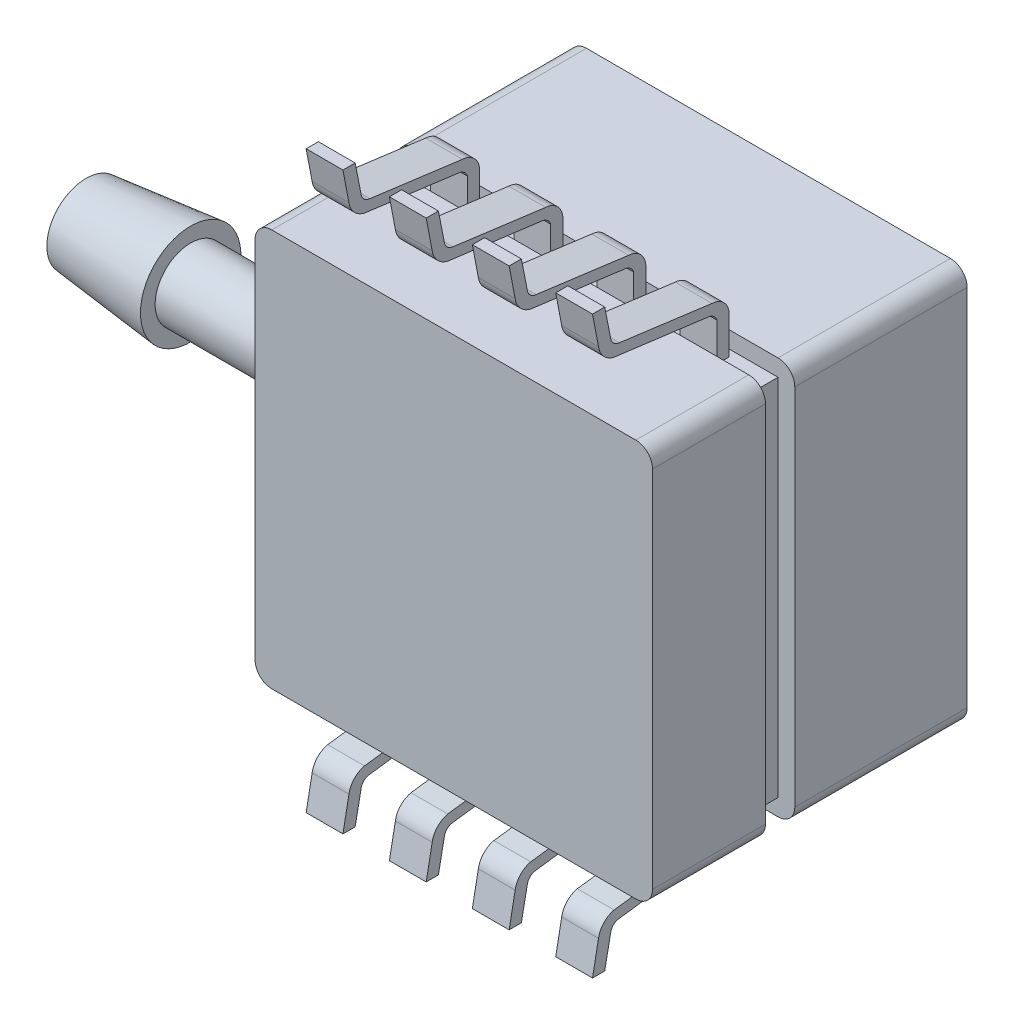
SolidWorks part; units mm, degrees
ref_plane "Front Plane" through (0, 0, 0) normal (0, 0, 1) x (1, 0, 0)
ref_plane "Top Plane" through (0, 0, 0) normal (0, 1, 0) x (1, 0, 0)
ref_plane "Right Plane" through (0, 0, 0) normal (1, 0, 0) x (0, 0, -1)
sketch "Sketch1" plane through (0, 0, 0) normal (0, 0, 1) x (1, 0, 0)
  line L1 (-6.0325, -6.0325) -> (6.0325, -6.0325)
  line L2 (-6.0325, -6.0325) -> (-6.0325, 6.0325)
  line L3 (-6.0325, 6.0325) -> (6.0325, 6.0325)
  line L4 (6.0325, -6.0325) -> (6.0325, 6.0325)
  line L5 (-6.0325, -6.0325) -> (6.0325, 6.0325) construction
  line L6 (-6.0325, 6.0325) -> (6.0325, -6.0325) construction
  point P1 (0, 0)
  dimension "D1" = 12.065
  dimension "D2" = 12.065
extrude "Boss-Extrude1" add sketch "Sketch1" along normal blind 9.5504
sketch "Sketch3" plane through (0, 6.0325, 0) normal (0, 1, 0) x (1, 0, 0)
  line L0 (37.8159, 86.4688) -> (213.1492, 86.4688) construction
  line L1 (-6.0325, -9.5504) -> (-6.0325, 0) construction
  line L2 (-5.5245, -5.2324) -> (-6.0325, -5.2324)
  line L3 (-5.5245, -5.2324) -> (-5.5245, -6.1214)
  line L4 (-5.5245, -6.1214) -> (-6.0325, -6.1214)
  line L5 (-6.0325, -5.2324) -> (-6.0325, -6.1214)
  line L6 (6.0325, -9.5504) -> (-6.0325, -9.5504) construction
  line L7 (0, 0) -> (0, -9.5504) construction
  line L8 (6.0325, -5.2324) -> (6.0325, -6.1214)
  line L9 (5.5245, -6.1214) -> (6.0325, -6.1214)
  line L10 (5.5245, -5.2324) -> (5.5245, -6.1214)
  line L11 (5.5245, -5.2324) -> (6.0325, -5.2324)
  dimension "D1" = 3.429
  dimension "D2" = 0.889
  dimension "D3" = 0.508
extrude "Cut-Extrude1" cut sketch "Sketch3" against normal through all
sketch "Sketch4" plane through (5.5245, 0, 0) normal (1, 0, 0) x (0, 0, -1)
  line L0 (-5.2324, -6.0325) -> (-5.2324, 6.0325) construction
  line L1 (-6.1214, 6.0325) -> (-5.2324, 6.0325)
  line L2 (-6.1214, 6.0325) -> (-6.1214, 5.5245)
  line L3 (-6.1214, 5.5245) -> (-5.2324, 5.5245)
  line L4 (-5.2324, 6.0325) -> (-5.2324, 5.5245)
  line L6 (-6.1214, -6.0325) -> (-5.2324, -6.0325)
  line L7 (-6.1214, -6.0325) -> (-6.1214, -5.5245)
  line L8 (-6.1214, -5.5245) -> (-5.2324, -5.5245)
  line L9 (-5.2324, -6.0325) -> (-5.2324, -5.5245)
  dimension "D1" = 0.508
  dimension "D2" = 0.508
extrude "Cut-Extrude2" cut sketch "Sketch4" against normal through all
sketch "Sketch5" plane through (6.0325, 0, 0) normal (1, 0, 0) x (0, 0, -1)
  line L0 (120.7784, 207.8165) -> (628.7784, 207.8165) construction
  line L1 (-5.4408, 5.5245) -> (-5.4408, 6.6427)
  line L2 (-6.1214, 5.5245) -> (-5.2324, 5.5245) construction
  line L3 (-5.8107, 5.5245) -> (-5.8107, 6.6769)
  line L4 (-6.0874, 6.8958) -> (-8.9346, 7.2659)
  line L5 (-5.9608, 7.194) -> (-8.7733, 7.5656)
  line L6 (-9.2194, 8.727) -> (-9.031, 7.774)
  line L7 (-9.5894, 8.727) -> (-9.4077, 7.774)
  line L8 (-9.2194, 8.727) -> (-9.5894, 8.727)
  line L9 (0, 0) -> (-9.4077, 0) construction
  line L10 (-5.4408, 5.5245) -> (-5.8107, 5.5245)
  line L11 (-9.2194, -8.727) -> (-9.5894, -8.727)
  line L12 (-9.2194, -8.727) -> (-9.031, -7.774)
  line L13 (-9.5894, -8.727) -> (-9.4077, -7.774)
  line L14 (-6.0874, -6.8958) -> (-8.9346, -7.2659)
  line L15 (-5.9608, -7.194) -> (-8.7733, -7.5656)
  line L16 (-5.8107, -5.5245) -> (-5.8107, -6.6769)
  line L17 (-5.4408, -5.5245) -> (-5.4408, -6.6427)
  line L18 (-5.4408, -5.5245) -> (-5.8107, -5.5245)
  arc A0 (-5.4408, 6.6427) -> (-5.9608, 7.194) centre (-5.993, 6.6427) ccw
  arc A1 (-5.8107, 6.6769) -> (-6.0874, 6.8958) centre (-6.1107, 6.5819) ccw
  arc A2 (-9.031, 7.774) -> (-8.7733, 7.5656) centre (-8.7504, 7.8573) ccw
  arc A3 (-8.9346, 7.2659) -> (-9.4077, 7.774) centre (-8.7968, 7.8685) cw
  arc A4 (-8.9346, -7.2659) -> (-9.4077, -7.774) centre (-8.7968, -7.8685) ccw
  arc A5 (-9.031, -7.774) -> (-8.7733, -7.5656) centre (-8.7504, -7.8573) cw
  arc A6 (-5.8107, -6.6769) -> (-6.0874, -6.8958) centre (-6.1107, -6.5819) cw
  arc A7 (-5.4408, -6.6427) -> (-5.9608, -7.194) centre (-5.993, -6.6427) cw
extrude "Boss-Extrude2" add sketch "Sketch5" against normal through all contours A3 L4 A1 L3 L10 L1 A0 L5 A2 L6 L8 L7 | A7 L17 L18 L16 A6 L14 A4 L13 L11 L12 A5 L15 region at (6.0325, 7.171, 7.3734) region at (6.0325, -7.171, 7.3734)
sketch "Sketch6" plane through (0, 0, 0) normal (0, 0, -1) x (-1, 0, 0)
  line L0 (-236.8164, 115.7312) -> (-236.8164, 623.0645) construction
  line L1 (-6.0325, 6.0325) -> (6.0325, 6.0325) construction
  line L2 (-4.2501, 6.0325) -> (-6.2606, 6.0325)
  line L3 (-4.2501, 6.0325) -> (-4.2501, 9.0805)
  line L4 (-4.2501, 9.0805) -> (-6.2606, 9.0805)
  line L5 (-6.2606, 6.0325) -> (-6.2606, 9.0805)
  line L6 (-6.0325, 0) -> (6.0325, 0) construction
  line L7 (-3.1325, 6.0325) -> (-1.7195, 6.0325)
  line L8 (-3.1325, 6.0325) -> (-3.1325, 9.0805)
  line L9 (-3.1325, 9.0805) -> (-1.7195, 9.0805)
  line L10 (-1.7195, 6.0325) -> (-1.7195, 9.0805)
  line L11 (-0.6019, 6.0325) -> (0.7988, 6.0325)
  line L12 (-0.6019, 6.0325) -> (-0.6019, 9.0805)
  line L13 (-0.6019, 9.0805) -> (0.7988, 9.0805)
  line L14 (0.7988, 6.0325) -> (0.7988, 9.0805)
  line L15 (1.9164, 6.0325) -> (3.3259, 6.0325)
  line L16 (1.9164, 6.0325) -> (1.9164, 9.0805)
  line L17 (1.9164, 9.0805) -> (3.3259, 9.0805)
  line L18 (3.3259, 6.0325) -> (3.3259, 9.0805)
  line L19 (4.4435, 6.0325) -> (6.1861, 6.0325)
  line L20 (4.4435, 6.0325) -> (4.4435, 9.0805)
  line L21 (4.4435, 9.0805) -> (6.1861, 9.0805)
  line L22 (6.1861, 6.0325) -> (6.1861, 9.0805)
  line L23 (-6.0325, -6.0325) -> (-6.0325, 6.0325) construction
  line L24 (6.0325, 6.0325) -> (6.0325, -6.0325) construction
  line L25 (4.4435, -6.0325) -> (6.1861, -6.0325)
  line L26 (1.9164, -6.0325) -> (3.3259, -6.0325)
  line L27 (-0.6019, -6.0325) -> (0.7988, -6.0325)
  line L28 (-3.1325, -6.0325) -> (-1.7195, -6.0325)
  line L29 (-4.2501, -6.0325) -> (-6.2606, -6.0325)
  line L30 (-4.2501, -9.0805) -> (-6.2606, -9.0805)
  line L31 (-3.1325, -9.0805) -> (-1.7195, -9.0805)
  line L32 (-0.6019, -9.0805) -> (0.7988, -9.0805)
  line L33 (1.9164, -9.0805) -> (3.3259, -9.0805)
  line L34 (4.4435, -9.0805) -> (6.1861, -9.0805)
  line L35 (6.1861, -6.0325) -> (6.1861, -9.0805)
  line L36 (4.4435, -6.0325) -> (4.4435, -9.0805)
  line L37 (3.3259, -6.0325) -> (3.3259, -9.0805)
  line L38 (1.9164, -6.0325) -> (1.9164, -9.0805)
  line L39 (0.7988, -6.0325) -> (0.7988, -9.0805)
  line L40 (-0.6019, -6.0325) -> (-0.6019, -9.0805)
  line L41 (-1.7195, -6.0325) -> (-1.7195, -9.0805)
  line L42 (-3.1325, -6.0325) -> (-3.1325, -9.0805)
  line L43 (-4.2501, -6.0325) -> (-4.2501, -9.0805)
  line L44 (-6.2606, -6.0325) -> (-6.2606, -9.0805)
  dimension "D1" = 3.048
  dimension "D2" = 1.1176
  dimension "D3" = 1.1176
  dimension "D4" = 1.1176
  dimension "D5" = 1.1176
extrude "Cut-Extrude3" cut sketch "Sketch6" against normal through all
sketch "Sketch7" plane through (0, 6.0325, 0) normal (0, 1, 0) x (1, 0, 0)
  line L0 (-4.4435, -5.4408) -> (-4.4435, -5.9608) construction
  line L1 (-6.0325, -5.4408) -> (-4.4435, -5.4408)
  line L2 (-6.0325, -5.4408) -> (-6.0325, -5.8107)
  line L3 (-6.0325, -5.8107) -> (-4.4435, -5.8107)
  line L4 (-4.4435, -5.4408) -> (-4.4435, -5.8107)
  line L5 (-4.4435, -5.8107) -> (-6.0325, -5.8107) construction
  line L7 (-3.3259, -5.4408) -> (-1.9164, -5.4408)
  line L8 (-3.3259, -5.4408) -> (-3.3259, -5.8107)
  line L9 (-3.3259, -5.8107) -> (-1.9164, -5.8107)
  line L10 (-1.9164, -5.4408) -> (-1.9164, -5.8107)
  line L11 (-0.7988, -5.4408) -> (0.6019, -5.4408)
  line L12 (-0.7988, -5.4408) -> (-0.7988, -5.8107)
  line L13 (-0.7988, -5.8107) -> (0.6019, -5.8107)
  line L14 (0.6019, -5.4408) -> (0.6019, -5.8107)
  line L15 (1.7195, -5.4408) -> (3.1325, -5.4408)
  line L16 (1.7195, -5.4408) -> (1.7195, -5.8107)
  line L17 (1.7195, -5.8107) -> (3.1325, -5.8107)
  line L18 (3.1325, -5.4408) -> (3.1325, -5.8107)
  line L19 (4.2501, -5.4408) -> (6.0325, -5.4408)
  line L20 (4.2501, -5.4408) -> (4.2501, -5.8107)
  line L21 (4.2501, -5.8107) -> (6.0325, -5.8107)
  line L22 (6.0325, -5.4408) -> (6.0325, -5.8107)
extrude "Cut-Extrude4" cut sketch "Sketch7" against normal up to surface (0.508 mm away) up to face at (0, 5.5245, 5.3366)
sketch "Sketch8" plane through (0, -6.0325, 0) normal (0, -1, 0) x (1, 0, 0)
  line L1 (-6.0325, 5.8107) -> (-4.4435, 5.8107)
  line L2 (-6.0325, 5.8107) -> (-6.0325, 5.4408)
  line L3 (-6.0325, 5.4408) -> (-4.4435, 5.4408)
  line L4 (-4.4435, 5.8107) -> (-4.4435, 5.4408)
  line L5 (-3.3259, 5.8107) -> (-1.9164, 5.8107)
  line L6 (-3.3259, 5.8107) -> (-3.3259, 5.4408)
  line L7 (-3.3259, 5.4408) -> (-1.9164, 5.4408)
  line L8 (-1.9164, 5.8107) -> (-1.9164, 5.4408)
  line L9 (-0.7988, 5.8107) -> (0.6019, 5.8107)
  line L10 (-0.7988, 5.8107) -> (-0.7988, 5.4408)
  line L11 (-0.7988, 5.4408) -> (0.6019, 5.4408)
  line L12 (0.6019, 5.8107) -> (0.6019, 5.4408)
  line L13 (1.7195, 5.8107) -> (3.1325, 5.8107)
  line L14 (1.7195, 5.8107) -> (1.7195, 5.4408)
  line L15 (1.7195, 5.4408) -> (3.1325, 5.4408)
  line L16 (3.1325, 5.8107) -> (3.1325, 5.4408)
  line L17 (4.2501, 5.8107) -> (6.0325, 5.8107)
  line L18 (4.2501, 5.8107) -> (4.2501, 5.4408)
  line L19 (4.2501, 5.4408) -> (6.0325, 5.4408)
  line L20 (6.0325, 5.8107) -> (6.0325, 5.4408)
extrude "Cut-Extrude5" cut sketch "Sketch8" against normal up to surface (0.508 mm away) up to face at (0, -5.5245, 5.966)
fillet "Fillet1" radius 0.508 8 edges at (6.0325, 6.0325, 2.6162) (6.0325, 6.0325, 7.8359) (-6.0325, 6.0325, 7.8359) (-6.0325, 6.0325, 2.6162) (-6.0325, -6.0325, 7.8359) (-6.0325, -6.0325, 2.6162) (6.0325, -6.0325, 7.8359) (6.0325, -6.0325, 2.6162)
sketch "Sketch9" plane through (-6.0325, 0, 0) normal (-1, 0, 0) x (0, 0, 1)
  line L2 (0, 5.5245) -> (0, -5.5245) construction
  circle A0 centre (1.2192, -2.159) radius 1.0795
  circle A1 centre (8.3312, 2.159) radius 1.0795
  circle A2 centre (8.3312, 2.159) radius 0.3969
  circle A3 centre (1.2192, -2.159) radius 0.3969
  dimension "D3" = 1.2192
  dimension "D5" = 2.159
  dimension "D6" = 2.159
  dimension "D7" = 0.7937
  dimension "D8" = 0.7937
  dimension "D1" = 7.112
  dimension "D2" = 4.318
  dimension "D4" = 2.159
extrude "Boss-Extrude3" add sketch "Sketch9" along normal blind 3.175
sketch "Sketch10" plane through (-9.2075, 0, 0) normal (-1, 0, 0) x (0, 0, 1)
  circle A0 centre (1.2192, -2.159) radius 0.3969
  circle A1 centre (1.2192, -2.159) radius 1.524
  circle A2 centre (8.3312, 2.159) radius 0.3969
  circle A3 centre (8.3312, 2.159) radius 1.524
  dimension "D1" = 3.048
  dimension "D2" = 3.048
sketch "Sketch11"
extrude "Boss-Extrude4" add sketch "Sketch10" along normal blind 3.175 separate body
chamfer "Chamfer1" distance 3.175 angle 6 1 edges at (-12.3825, 2.159, 9.8552) first distance on face at (-12.3825, 2.159, 9.8552)
chamfer "Chamfer2" distance 3.175 angle 6 1 edges at (-12.3825, -2.159, 2.7432) first distance on face at (-12.3825, -2.159, 2.7432)
